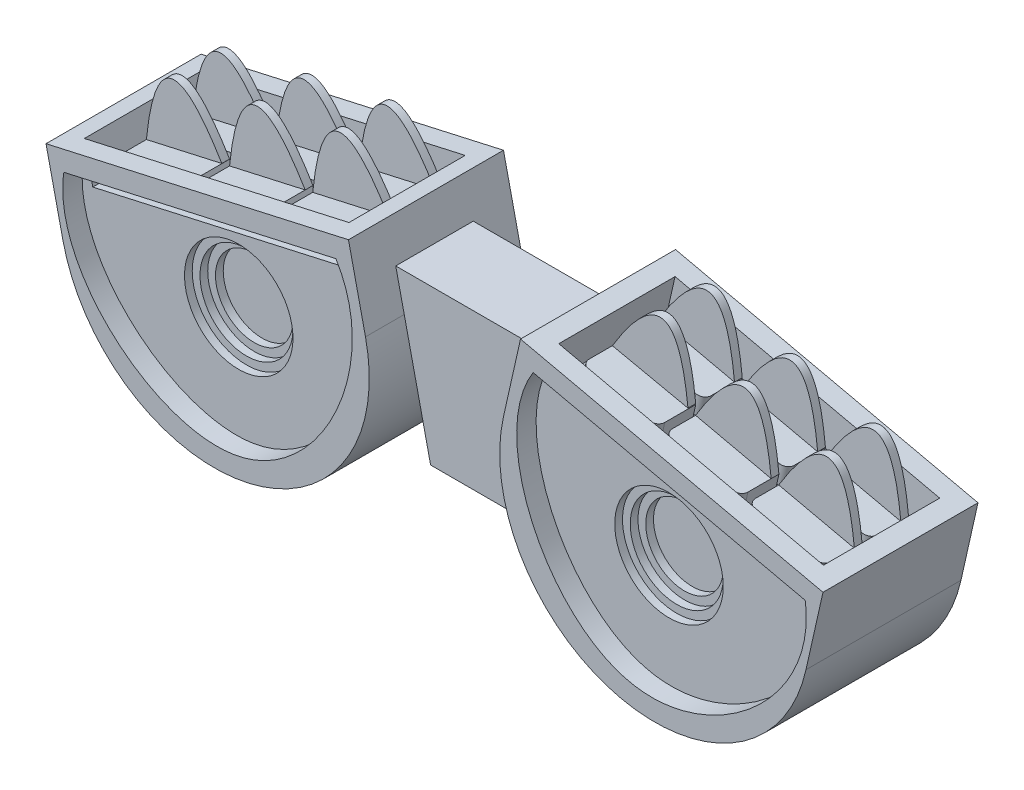
SolidWorks part; units mm, degrees
ref_plane "Front Plane" through (0, 0, 0) normal (0, 0, 1) x (1, 0, 0)
ref_plane "Top Plane" through (0, 0, 0) normal (0, 1, 0) x (1, 0, 0)
ref_plane "Right Plane" through (0, 0, 0) normal (1, 0, 0) x (0, 0, -1)
sketch "Sketch1" plane through (0, 0, 0) normal (0, 1, 0) x (1, 0, 0)
  line L1 (-17.1532, -29.0896) -> (2.8468, -29.0896)
  line L2 (-17.1532, -29.0896) -> (-17.1532, -39.0896)
  line L3 (-17.1532, -39.0896) -> (2.8468, -39.0896)
  line L4 (2.8468, -29.0896) -> (2.8468, -39.0896)
  dimension "D1" = 20
  dimension "D2" = 10
extrude "Boss-Extrude1" add sketch "Sketch1" along normal blind 20
sketch "Sketch2" plane through (0, 0, 39.0896) normal (0, 0, 1) x (1, 0, 0)
  line L3 (-17.1532, 20) -> (-17.1532, 0)
  line L6 (2.8468, 0) -> (2.8468, 20)
  line L7 (-17.1532, 0) -> (-12.6532, 0)
  line L8 (-17.1532, 0) -> (2.8468, 0) construction
  line L9 (-12.6532, 0) -> (-17.1532, 20)
  line L10 (2.8468, 0) -> (-1.6532, 0)
  line L11 (-1.6532, 0) -> (2.8468, 20)
  dimension "D1" = 4.5
  dimension "D2" = 4.5
extrude "Cut-Extrude1" cut sketch "Sketch2" against normal blind 10
sketch "Sketch6" plane through (-1.5736, 0.3541, 0) normal (0.9756, -0.2195, 0) x (0, 0, -1)
  line L0 (-39.0896, 20.1371) -> (-29.0896, 20.1371) construction
  line L1 (-44.0896, 25.1371) -> (-24.0896, 25.1371)
  line L2 (-44.0896, 25.1371) -> (-44.0896, 15.1371)
  line L3 (-44.0896, 15.1371) -> (-24.0896, 15.1371)
  line L4 (-24.0896, 25.1371) -> (-24.0896, 15.1371)
  line L5 (-39.0896, 20.1371) -> (-39.0896, -0.3629) construction
  dimension "D1" = 20
  dimension "D2" = 10
  dimension "D3" = 5
  dimension "D4" = 5
extrude "Boss-Extrude4" add sketch "Sketch6" along normal blind 40
sketch "Sketch8" plane through (0, 0, 44.0896) normal (0, 0, 1) x (1, 0, 0)
  line L0 (40.7736, 6.3415) -> (1.7492, 15.122) construction
  line L1 (1.7492, 15.122) -> (-1.6532, 0) construction
  line L2 (1.7492, 15.122) -> (40.7736, 6.3415)
  arc A0 (40.7736, 6.3415) -> (1.7492, 15.122) centre (21.2614, 10.7317) cw
extrude "Boss-Extrude5" add sketch "Sketch8" against normal blind 20
ref_axis "Axis3" through (-7.1532, 20, 29.0896) along (0, 0, 1)
ref_axis "Axis4" through (-7.1532, 0, 39.0896) along (0, 0, -1)
ref_plane "Plane2" through (-7.1532, 0, 0) normal (1, 0, 0) x (0, 0, -1)
mirror "Mirror2" about plane through (-7.1532, 0, 0) normal (1, 0, 0) of "Boss-Extrude5", "Boss-Extrude4"
sketch "Sketch17" plane through (0, 0, 0) normal (0, -1, 0) x (1, 0, 0)
  line L0 (-7.1532, -5.5) -> (-7.1532, 5.5) construction
  line L1 (-12.6532, 39.0896) -> (-1.6532, 39.0896) construction
  circle A0 centre (-7.1532, 34.0896) radius 2.5
  dimension "D1" = 5
extrude "Cut-Extrude9" cut sketch "Sketch17" against normal blind 10
ref_axis "Axis1" through (-7.1532, 20, 29.0896) along (0, 0, 1)
ref_axis "Axis2" through (-7.1532, 0, 39.0896) along (0, 0, -1)
ref_plane "Plane1" through (-7.1532, 0, 0) normal (1, 0, 0) x (0, 0, -1)
sketch "Sketch18" plane through (0, 0, 44.0896) normal (0, 0, 1) x (1, 0, 0)
  line L0 (5.5703, 21.9497) -> (40.67, 14.0523)
  line L2 (42.9687, 16.0976) -> (3.9443, 24.878) construction
  spline S0 degree 3 poles (40.67, 14.0523) (42.3339, 2.7931) (14.9447, -20.2714) (-0.479, 12.2746) (5.5703, 21.9497) knots 0 0 0 0 0.496132 1 1 1 1
  dimension "D1" = 2.5
extrude "Cut-Extrude10" cut sketch "Sketch18" against normal blind 2.5
sketch "Sketch22" plane through (0, 0, 41.5896) normal (0, 0, 1) x (1, 0, 0)
  line L0 (42.9687, 16.0976) -> (3.9443, 24.878) construction
  line L1 (42.9687, 16.0976) -> (40.7736, 6.3415) construction
  circle A0 centre (20.6029, 7.8049) radius 7
  dimension "D1" = 13
  dimension "D2" = 20
extrude "Cut-Extrude11" cut sketch "Sketch22" against normal blind 1
ref_point "Point2"
sketch "Sketch24" plane through (0, 0, 40.5896) normal (0, 0, 1) x (1, 0, 0)
  circle A0 centre (20.6029, 7.8049) radius 6
extrude "Cut-Extrude12" cut sketch "Sketch24" against normal blind 1
sketch "Sketch25" plane through (0, 0, 39.5896) normal (0, 0, 1) x (1, 0, 0)
  circle A0 centre (20.6029, 7.8049) radius 5
extrude "Cut-Extrude13" cut sketch "Sketch25" against normal blind 1 contours A0
mirror "Mirror3" about plane through (-7.1532, 0, 0) normal (1, 0, 0) of "Cut-Extrude13", "Cut-Extrude12", "Cut-Extrude11", "Cut-Extrude10"
sketch "Sketch26" plane through (5.5179, 24.524, 0) normal (0.2195, 0.9756, 0) x (0.9756, -0.2195, 0)
  line L0 (38.3871, -24.0896) -> (-1.6129, -24.0896) construction
  line L1 (0.8871, -26.5896) -> (35.8871, -26.5896)
  line L2 (0.8871, -26.5896) -> (0.8871, -41.5896)
  line L3 (0.8871, -41.5896) -> (35.8871, -41.5896)
  line L4 (35.8871, -26.5896) -> (35.8871, -41.5896)
  line L5 (-1.6129, -24.0896) -> (-1.6129, -44.0896) construction
  dimension "D1" = 35
  dimension "D2" = 15
  dimension "D3" = 2.5
  dimension "D4" = 2.5
extrude "Cut-Extrude14" cut sketch "Sketch26" against normal blind 5 contours L1 L4 L3 L2
sketch "Sketch27" plane through (4.4203, 19.6459, 0) normal (0.2195, 0.9756, 0) x (0.9756, -0.2195, 0)
  line L0 (0.8871, -26.5896) -> (35.8871, -26.5896) construction
  line L1 (2.3871, -28.5896) -> (12.3871, -28.5896)
  line L2 (2.3871, -28.5896) -> (2.3871, -32.5896)
  line L3 (3.3871, -33.5896) -> (11.3871, -33.5896)
  line L4 (12.3871, -28.5896) -> (12.3871, -32.5896)
  line L5 (35.8871, -26.5896) -> (35.8871, -41.5896) construction
  line L6 (13.3871, -28.5896) -> (23.3871, -28.5896)
  line L7 (13.3871, -28.5896) -> (13.3871, -32.5896)
  line L8 (14.3871, -33.5896) -> (22.3871, -33.5896)
  line L9 (23.3871, -28.5896) -> (23.3871, -32.5896)
  line L10 (24.3871, -28.5896) -> (34.3871, -28.5896)
  line L11 (24.3871, -28.5896) -> (24.3871, -32.5896)
  line L12 (25.3871, -33.5896) -> (33.3871, -33.5896)
  line L13 (34.3871, -28.5896) -> (34.3871, -32.5896)
  line L18 (2.3871, -34.5896) -> (12.3871, -34.5896)
  line L19 (2.3871, -34.5896) -> (2.3871, -38.5896)
  line L20 (3.3871, -39.5896) -> (11.3871, -39.5896)
  line L21 (12.3871, -34.5896) -> (12.3871, -38.5896)
  line L22 (13.3871, -34.5896) -> (23.3871, -34.5896)
  line L23 (13.3871, -34.5896) -> (13.3871, -38.5896)
  line L24 (14.3871, -39.5896) -> (22.3871, -39.5896)
  line L25 (23.3871, -34.5896) -> (23.3871, -38.5896)
  line L26 (24.3871, -34.5896) -> (34.3871, -34.5896)
  line L27 (24.3871, -34.5896) -> (24.3871, -38.5896)
  line L28 (25.3871, -39.5896) -> (33.3871, -39.5896)
  line L29 (34.3871, -34.5896) -> (34.3871, -38.5896)
  arc A0 (33.3871, -33.5896) -> (34.3871, -32.5896) centre (33.3871, -32.5896) ccw
  arc A1 (33.3871, -39.5896) -> (34.3871, -38.5896) centre (33.3871, -38.5896) ccw
  arc A2 (24.3871, -38.5896) -> (25.3871, -39.5896) centre (25.3871, -38.5896) ccw
  arc A3 (24.3871, -32.5896) -> (25.3871, -33.5896) centre (25.3871, -32.5896) ccw
  arc A4 (2.3871, -38.5896) -> (3.3871, -39.5896) centre (3.3871, -38.5896) ccw
  arc A5 (11.3871, -39.5896) -> (12.3871, -38.5896) centre (11.3871, -38.5896) ccw
  arc A6 (22.3871, -39.5896) -> (23.3871, -38.5896) centre (22.3871, -38.5896) ccw
  arc A7 (13.3871, -38.5896) -> (14.3871, -39.5896) centre (14.3871, -38.5896) ccw
  arc A8 (22.3871, -33.5896) -> (23.3871, -32.5896) centre (22.3871, -32.5896) ccw
  arc A9 (13.3871, -32.5896) -> (14.3871, -33.5896) centre (14.3871, -32.5896) ccw
  arc A10 (11.3871, -33.5896) -> (12.3871, -32.5896) centre (11.3871, -32.5896) ccw
  arc A11 (2.3871, -32.5896) -> (3.3871, -33.5896) centre (3.3871, -32.5896) ccw
  point P38 (2.3871, -39.5896)
  point P41 (12.3871, -39.5896)
  point P52 (12.3871, -33.5896)
  dimension "D12" = 1
  dimension "D1" = 10
  dimension "D2" = 5
  dimension "D3" = 2
  dimension "D4" = 10
  dimension "D5" = 1
  dimension "D6" = 10
  dimension "D7" = 1
  dimension "D8" = 1.5
  dimension "D9" = 10
  dimension "D10" = 5
  dimension "D11" = 1
extrude "Boss-Extrude6" add sketch "Sketch27" along normal blind 2.5
sketch "Sketch28" plane through (0, 0, 28.5896) normal (0, 0, -1) x (-1, 0, 0)
  line L0 (-17.0541, 19.3659) -> (-7.298, 21.561) construction
  line L1 (-27.7858, 16.9512) -> (-18.0297, 19.1463) construction
  line L2 (-38.5175, 14.5366) -> (-28.7614, 16.7317) construction
  line L3 (-7.298, 21.561) -> (-17.0541, 19.3659)
  line L4 (-18.0297, 19.1463) -> (-27.7858, 16.9512)
  line L5 (-28.7614, 16.7317) -> (-38.5175, 14.5366)
  spline S0 degree 2 poles (-7.298, 21.561) (-15.4687, 35.0976) (-17.0541, 19.3659) knots 0 0 0 1 1 1
  spline S1 degree 2 poles (-18.0297, 19.1463) (-26.2004, 32.6829) (-27.7858, 16.9512) knots 0 0 0 1 1 1
  spline S2 degree 2 poles (-38.5175, 14.5366) (-36.9321, 30.2683) (-28.7614, 16.7317) knots 0 0 0 1 1 1
  dimension "D1" = 7.5
  dimension "D2" = 7.5
  dimension "D3" = 7.5
extrude "Boss-Extrude7" add sketch "Sketch28" against normal blind 1
sketch "Sketch29" plane through (0, 0, 34.5896) normal (0, 0, -1) x (-1, 0, 0)
  line L0 (-17.0541, 19.3659) -> (-7.298, 21.561) construction
  line L1 (-27.7858, 16.9512) -> (-18.0297, 19.1463) construction
  line L2 (-38.5175, 14.5366) -> (-28.7614, 16.7317) construction
  line L3 (-7.298, 21.561) -> (-17.0491, 19.4625)
  line L4 (-18.0297, 19.1463) -> (-27.7858, 16.9512)
  line L5 (-28.7614, 16.7317) -> (-38.5175, 14.5366)
  spline S0 degree 2 poles (-7.298, 21.561) (-15.4213, 35.0604) (-17.0491, 19.4625) knots 0 0 0 1 1 1
  spline S1 degree 2 poles (-18.0297, 19.1463) (-26.2004, 32.6829) (-27.7858, 16.9512) knots 0 0 0 1 1 1
  spline S2 degree 2 poles (-28.7614, 16.7317) (-36.9321, 30.2683) (-38.5175, 14.5366) knots 0 0 0 1 1 1
  dimension "D1" = 7.5
  dimension "D2" = 7.5
  dimension "D3" = 7.5
extrude "Boss-Extrude8" add sketch "Sketch29" against normal blind 1
mirror "Mirror7" about plane through (-7.1532, 0, 0) normal (1, 0, 0) of "Cut-Extrude14"
sketch "Sketch30" plane through (-5.1097, 22.7098, 0) normal (-0.2195, 0.9756, 0) x (0.9756, 0.2195, 0)
  line L0 (-14.8446, -26.5896) -> (-49.8446, -26.5896) construction
  line L1 (-48.3446, -28.5896) -> (-38.3446, -28.5896)
  line L2 (-48.3446, -28.5896) -> (-48.3446, -32.5896)
  line L3 (-47.3446, -33.5896) -> (-39.3446, -33.5896)
  line L4 (-38.3446, -28.5896) -> (-38.3446, -32.5896)
  line L5 (-37.3446, -28.5896) -> (-27.3446, -28.5896)
  line L6 (-37.3446, -28.5896) -> (-37.3446, -32.8029)
  line L7 (-36.3446, -33.8029) -> (-28.3446, -33.8029)
  line L8 (-27.3446, -28.5896) -> (-27.3446, -32.8029)
  line L9 (-26.3446, -28.5896) -> (-16.3446, -28.5896)
  line L10 (-26.3446, -28.5896) -> (-26.3446, -32.8029)
  line L11 (-25.3446, -33.8029) -> (-17.3446, -33.8029)
  line L12 (-16.3446, -28.5896) -> (-16.3446, -32.8029)
  line L13 (-48.3446, -34.5896) -> (-38.3446, -34.5896)
  line L14 (-48.3446, -34.5896) -> (-48.3446, -38.5896)
  line L15 (-47.3446, -39.5896) -> (-39.3446, -39.5896)
  line L16 (-38.3446, -34.5896) -> (-38.3446, -38.5896)
  line L17 (-37.3446, -34.5896) -> (-27.3446, -34.5896)
  line L18 (-37.3446, -34.5896) -> (-37.3446, -38.6811)
  line L19 (-36.3446, -39.6811) -> (-28.3446, -39.6811)
  line L20 (-27.3446, -34.5896) -> (-27.3446, -38.6811)
  line L21 (-26.3446, -34.5896) -> (-16.3446, -34.5896)
  line L22 (-26.3446, -34.5896) -> (-26.3446, -38.6811)
  line L23 (-25.3446, -39.6811) -> (-17.3446, -39.6811)
  line L24 (-16.3446, -34.5896) -> (-16.3446, -38.6811)
  line L26 (-49.8446, -26.5896) -> (-49.8446, -41.5896) construction
  arc A0 (-37.3446, -32.8029) -> (-36.3446, -33.8029) centre (-36.3446, -32.8029) ccw
  arc A1 (-28.3446, -33.8029) -> (-27.3446, -32.8029) centre (-28.3446, -32.8029) ccw
  arc A2 (-17.3446, -33.8029) -> (-16.3446, -32.8029) centre (-17.3446, -32.8029) ccw
  arc A3 (-26.3446, -32.8029) -> (-25.3446, -33.8029) centre (-25.3446, -32.8029) ccw
  arc A4 (-17.3446, -39.6811) -> (-16.3446, -38.6811) centre (-17.3446, -38.6811) ccw
  arc A5 (-26.3446, -38.6811) -> (-25.3446, -39.6811) centre (-25.3446, -38.6811) ccw
  arc A6 (-28.3446, -39.6811) -> (-27.3446, -38.6811) centre (-28.3446, -38.6811) ccw
  arc A7 (-37.3446, -38.6811) -> (-36.3446, -39.6811) centre (-36.3446, -38.6811) ccw
  arc A8 (-39.3446, -39.5896) -> (-38.3446, -38.5896) centre (-39.3446, -38.5896) ccw
  arc A9 (-48.3446, -38.5896) -> (-47.3446, -39.5896) centre (-47.3446, -38.5896) ccw
  arc A10 (-39.3446, -33.5896) -> (-38.3446, -32.5896) centre (-39.3446, -32.5896) ccw
  arc A11 (-48.3446, -32.5896) -> (-47.3446, -33.5896) centre (-47.3446, -32.5896) ccw
  point P48 (-48.3446, -39.5896)
  point P53 (-48.3446, -33.5896)
  dimension "D16" = 1
  dimension "D1" = 10
  dimension "D2" = 10
  dimension "D3" = 10
  dimension "D4" = 10
  dimension "D5" = 10
  dimension "D6" = 10
  dimension "D7" = 1
  dimension "D8" = 1
  dimension "D9" = 1
  dimension "D10" = 1
  dimension "D11" = 1
  dimension "D12" = 5
  dimension "D13" = 5
  dimension "D14" = 2
  dimension "D15" = 1.5
extrude "Boss-Extrude9" add sketch "Sketch30" along normal blind 2.5
sketch "Sketch31" plane through (0, 0, 28.5896) normal (0, 0, -1) x (-1, 0, 0)
  line L0 (43.0679, 16.7317) -> (52.824, 14.5366) construction
  line L1 (32.3362, 19.1463) -> (42.0923, 16.9512) construction
  line L2 (21.6045, 21.561) -> (31.3606, 19.3659) construction
  line L3 (52.824, 14.5366) -> (43.0679, 16.7317)
  line L4 (42.0923, 16.9512) -> (32.3362, 19.1463)
  line L5 (31.3606, 19.3659) -> (21.6045, 21.561)
  spline S0 degree 2 poles (52.824, 14.5366) (51.2386, 30.2683) (43.0679, 16.7317) knots 0 0 0 1 1 1
  spline S1 degree 2 poles (42.0923, 16.9512) (40.5069, 32.6829) (32.3362, 19.1463) knots 0 0 0 1 1 1
  spline S2 degree 2 poles (31.3606, 19.3659) (29.7752, 35.0976) (21.6045, 21.561) knots 0 0 0 1 1 1
  dimension "D1" = 7.5
  dimension "D2" = 7.5
  dimension "D3" = 7.5
sketch "Sketch32" plane through (0, 0, 34.5896) normal (0, 0, -1) x (-1, 0, 0)
  line L0 (43.0679, 16.7317) -> (52.824, 14.5366) construction
  line L2 (32.3362, 19.1463) -> (42.0923, 16.9512) construction
  line L3 (43.0933, 16.726) -> (52.824, 14.5366)
  line L4 (32.3362, 19.1463) -> (42.0923, 16.9512)
  line L5 (21.6045, 21.561) -> (31.3606, 19.3659) construction
  line L6 (21.6045, 21.561) -> (31.3606, 19.3659)
  spline S0 degree 2 poles (52.824, 14.5366) (51.2337, 30.2694) (43.0933, 16.726) knots 0 0 0 1 1 1
  spline S1 degree 2 poles (42.0923, 16.9512) (40.5069, 32.6829) (32.3362, 19.1463) knots 0 0 0 1 1 1
  spline S2 degree 2 poles (21.6045, 21.561) (29.7752, 35.0976) (31.3606, 19.3659) knots 0 0 0 1 1 1
  dimension "D1" = 7.5
  dimension "D2" = 7.5
  dimension "D3" = 7.5
extrude "Boss-Extrude10" add sketch "Sketch31" against normal blind 1
extrude "Boss-Extrude11" add sketch "Sketch32" against normal blind 1
